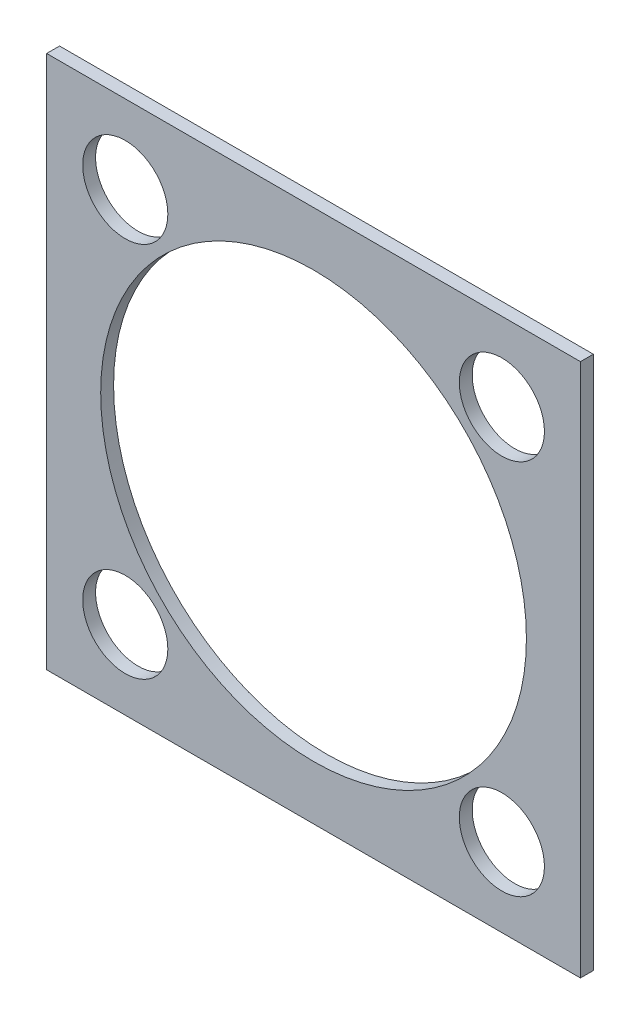
SolidWorks part; units mm, degrees
ref_plane "Front Plane" through (0, 0, 0) normal (0, 0, 1) x (1, 0, 0)
ref_plane "Top Plane" through (0, 0, 0) normal (0, 1, 0) x (1, 0, 0)
ref_plane "Right Plane" through (0, 0, 0) normal (1, 0, 0) x (0, 0, -1)
sketch "Sketch1" plane through (0, 0, 0) normal (0, 0, 1) x (1, 0, 0)
  line L1 (-20.701, 20.701) -> (20.701, 20.701)
  line L2 (-20.701, 20.701) -> (-20.701, -20.701)
  line L3 (-20.701, -20.701) -> (20.701, -20.701)
  line L4 (20.701, 20.701) -> (20.701, -20.701)
  dimension "D1" = 41.402
  dimension "D2" = 41.402
  dimension "D3" = 20.701
  dimension "D4" = 20.701
extrude "Boss-Extrude1" add sketch "Sketch1" along normal blind 0.5 and the other way blind 0.5
sketch "Sketch2" plane through (0, 0, 0) normal (0, 0, 1) x (1, 0, 0)
  line L1 (-20.701, 20.701) -> (-23.9293, 20.701)
  line L2 (-20.701, 20.701) -> (-20.701, 14.351)
  line L3 (-20.701, 14.351) -> (-23.9293, 14.351)
  line L4 (-23.9293, 20.701) -> (-23.9293, 14.351)
  line L5 (20.701, -20.701) -> (23.9293, -20.701)
  line L6 (20.701, -20.701) -> (20.701, -14.351)
  line L7 (20.701, -14.351) -> (23.9293, -14.351)
  line L8 (23.9293, -20.701) -> (23.9293, -14.351)
  dimension "D1" = 6.35
  dimension "D2" = 3.2283
  dimension "D3" = 3.2283
  dimension "D4" = 6.35
extrude "Boss-Extrude2" [suppressed] add sketch "Sketch2" along normal blind 0.5 and the other way blind 0.5
sketch "Sketch3" plane through (0, 0, 0.5) normal (0, 0, 1) x (1, 0, 0)
  circle A0 centre (0, 0) radius 16.51
  dimension "D1" = 33.02
extrude "Cut-Extrude1" cut sketch "Sketch3" against normal through all
sketch "Sketch6" plane through (0, 0, 0.5) normal (0, 0, 1) x (1, 0, 0)
  circle A0 centre (-14.605, 14.605) radius 3.302
  circle A1 centre (14.605, 14.605) radius 3.302
  dimension "D1" = 6.604
  dimension "D2" = 6.604
  dimension "D3" = 29.21
  dimension "D4" = 14.605
  dimension "D5" = 14.605
  dimension "D6" = 14.605
extrude "Cut-Extrude2" cut sketch "Sketch6" against normal through all
mirror "Mirror1" about plane through (0, 0, 0) normal (0, 1, 0) of "Cut-Extrude2"
sketch "Sketch4" plane through (0, 0, 0.5) normal (0, 0, 1) x (1, 0, 0)
  circle A0 centre (0, 0) radius 14.2875
  circle A1 centre (0, 0) radius 12.7
  dimension "D1" = 28.575
extrude "Boss-Extrude3" [suppressed] add sketch "Sketch4" along normal blind 0.0508
sketch "Sketch5" [suppressed] plane through (0, 0, 0.5) normal (0, 0, 1) x (1, 0, 0)
  line L1 (-23.9293, 20.701) -> (-20.701, 20.701)
  line L2 (-23.9293, 20.701) -> (-23.9293, 14.351)
  line L3 (-23.9293, 14.351) -> (-20.701, 14.351)
  line L4 (-20.701, 20.701) -> (-20.701, 14.351)
  line L5 (23.9293, -20.701) -> (20.701, -20.701)
  line L6 (23.9293, -20.701) -> (23.9293, -14.351)
  line L7 (23.9293, -14.351) -> (20.701, -14.351)
  line L8 (20.701, -20.701) -> (20.701, -14.351)
extrude "Boss-Extrude4" [suppressed] add sketch "Sketch5" along normal blind 0.0508
equation "\"D2@Sketch1\"=\"D1@Sketch1\""
equation "\"D3@Sketch1\"=\"D1@Sketch1\"/2"
equation "\"D4@Sketch1\"=\"D2@Sketch1\"/2"
equation "\"D4@Sketch6\"=\"D3@Sketch6\"/2"
equation "\"D5@Sketch6\"=\"D4@Sketch6\""
equation "\"D6@Sketch6\"=\"D4@Sketch6\""
